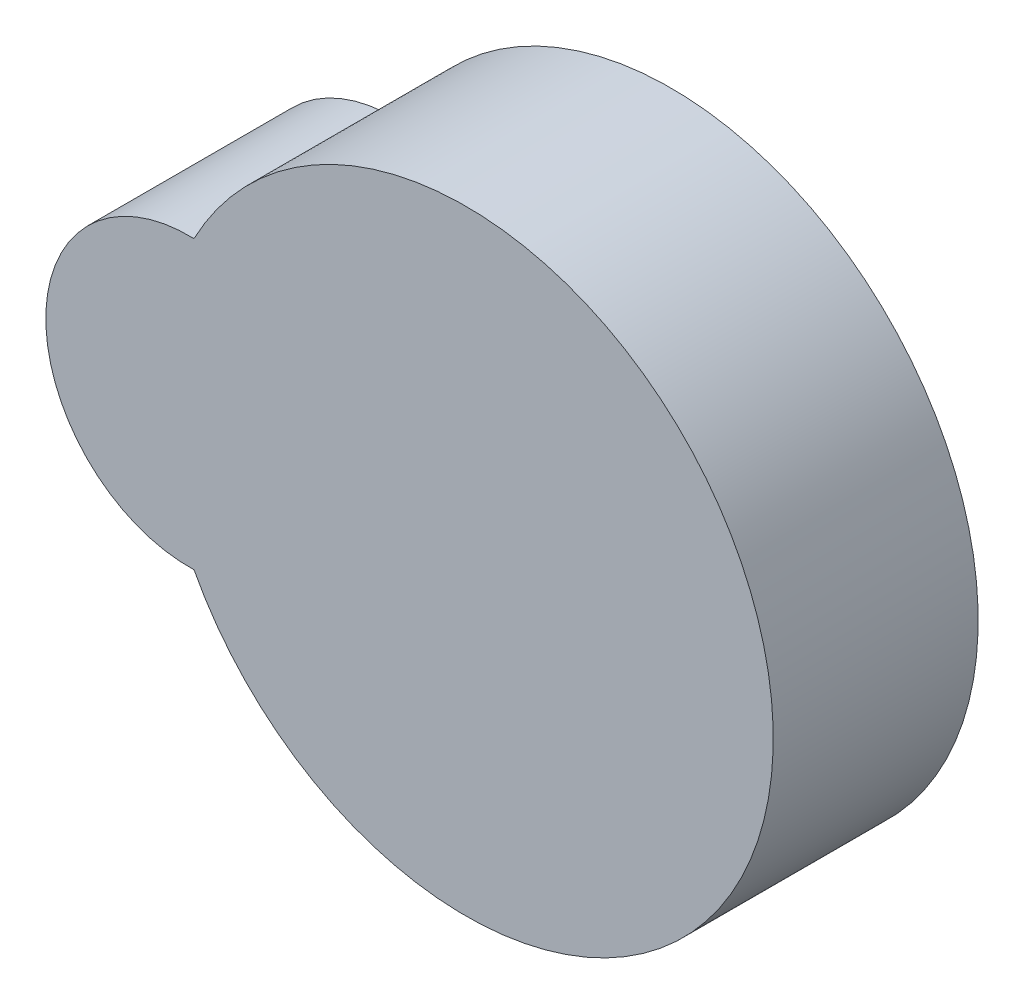
SolidWorks part; units mm, degrees
ref_plane "正面" through (0, 0, 0) normal (0, 0, 1) x (1, 0, 0)
ref_plane "平面" through (0, 0, 0) normal (0, 1, 0) x (1, 0, 0)
ref_plane "右側面" through (0, 0, 0) normal (1, 0, 0) x (0, 0, -1)
sketch "ｽｹｯﾁ1" plane through (0, 0, 0) normal (0, 0, 1) x (1, 0, 0)
  line L1 (0, 38.0232) -> (0, 0) construction
  line L2 (0, 0) -> (40.5262, 0) construction
  circle A0 centre (0, 0) radius 15
  circle A1 centre (-13.5, 0) radius 7
  dimension "D1" = 30
  dimension "D2" = 14
  dimension "D3" = 13.5
extrude "ﾎﾞｽ - 押し出し1" add sketch "ｽｹｯﾁ1" along normal blind 10 contours A1 | A0
